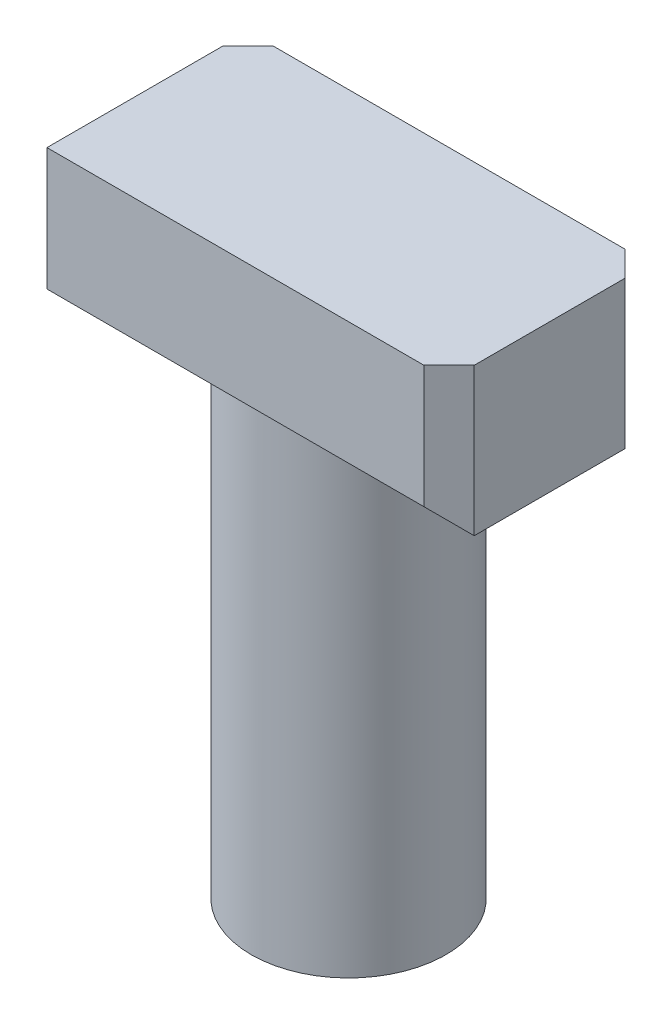
SolidWorks part; units mm, degrees
ref_plane "Front Plane" through (0, 0, 0) normal (0, 0, 1) x (1, 0, 0)
ref_plane "Top Plane" through (0, 0, 0) normal (0, 1, 0) x (1, 0, 0)
ref_plane "Right Plane" through (0, 0, 0) normal (1, 0, 0) x (0, 0, -1)
sketch "Sketch1" plane through (0, 0, 0) normal (0, 1, 0) x (1, 0, 0)
  circle A0 centre (0, 1.5071) radius 6.15
  dimension "D1" = 12.3
extrude "Boss-Extrude1" add sketch "Sketch1" along normal blind 28.575
sketch "Sketch3" plane through (0, 28.575, 0) normal (0, 1, 0) x (1, 0, 0)
  line L0 (0, 7.6571) -> (0, -4.6429) construction
  line L2 (12.7, -4.8429) -> (-12.7, -4.8429)
  line L3 (12.7, -4.8429) -> (12.7, 7.8571)
  line L4 (12.7, 7.8571) -> (-12.7, 7.8571)
  line L5 (-12.7, -4.8429) -> (-12.7, 7.8571)
  line L6 (12.7, -4.8429) -> (-12.7, 7.8571) construction
  line L7 (12.7, 7.8571) -> (-12.7, -4.8429) construction
  circle A0 centre (0, 1.5071) radius 6.15 construction
  point P5 (0, 1.5071)
  dimension "D1" = 12.7
  dimension "D2" = 25.4
extrude "Boss-Extrude2" add sketch "Sketch3" along normal blind 9.325
chamfer "Chamfer1" distance 1.5875 angle 45 6 edges at (12.7, 33.2375, 4.8429) (0, 28.575, 4.8429) (-12.7, 28.575, -1.5071) (12.7, 33.2375, -7.8571) (-12.7, 33.2375, -7.8571) (0, 28.575, -7.8571)
